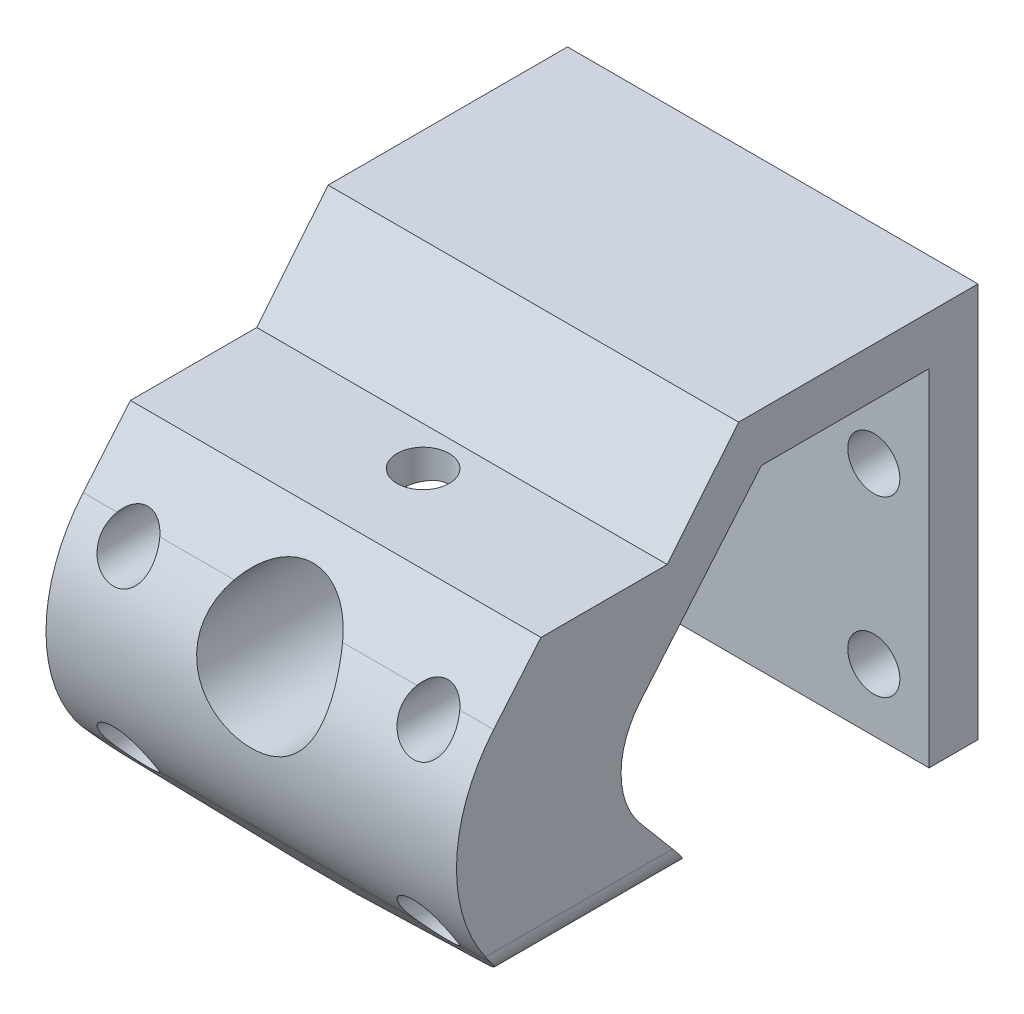
SolidWorks part; units mm, degrees
ref_plane "前视基准面" through (0, 0, 0) normal (0, 0, 1) x (1, 0, 0)
ref_plane "上视基准面" through (0, 0, 0) normal (0, 1, 0) x (1, 0, 0)
ref_plane "右视基准面" through (0, 0, 0) normal (1, 0, 0) x (0, 0, -1)
sketch "草图1" plane through (0, 0, 0) normal (1, 0, 0) x (0, 0, -1)
  line L0 (14.1075, 12.25) -> (3.7806, 12.25)
  line L1 (3.7806, 12.25) -> (-3.8242, 3.2211)
  line L2 (-3.8242, -3.2211) -> (3.7806, -12.25)
  line L3 (3.7806, -12.25) -> (14.1075, -12.25)
  line L4 (14.1075, -12.25) -> (14.1075, -9.25)
  line L5 (14.1075, -9.25) -> (9.3075, -9.25)
  line L6 (9.3075, -9.25) -> (9.3075, 9.25)
  line L7 (9.3075, 9.25) -> (14.1075, 9.25)
  line L8 (14.1075, 9.25) -> (14.1075, 12.25)
  line L9 (0, 0) -> (9.3075, 0) construction
  line L10 (14.3075, 12.45) -> (3.6876, 12.45)
  line L11 (3.6876, 12.45) -> (-3.9772, 3.3499)
  line L12 (-3.9772, -3.3499) -> (3.6876, -12.45)
  line L13 (3.6876, -12.45) -> (14.3075, -12.45)
  line L14 (14.3075, -12.45) -> (14.3075, -9.05)
  line L15 (14.3075, -9.05) -> (9.5075, -9.05)
  line L16 (9.5075, -9.05) -> (9.5075, 9.05)
  line L17 (9.5075, 9.05) -> (14.3075, 9.05)
  line L18 (14.3075, 9.05) -> (14.3075, 12.45)
  line L19 (0, -0.2) -> (9.3075, -0.2)
  line L20 (17.4075, 15.55) -> (2.2455, 15.55)
  line L21 (2.2455, 15.55) -> (-6.3482, 5.347)
  line L22 (-6.3482, -5.347) -> (2.2455, -15.55)
  line L23 (2.2455, -15.55) -> (17.4075, -15.55)
  line L24 (17.4075, -15.55) -> (17.4075, -5.95)
  line L28 (17.4075, 5.95) -> (17.4075, 15.55)
  line L29 (12.6075, 5.95) -> (17.4075, 5.95) construction
  line L30 (17.4075, -5.95) -> (12.6075, -5.95) construction
  line L31 (12.6075, -5.95) -> (12.6075, 5.95) construction
  line L32 (17.4075, 5.95) -> (17.4075, -5.95)
  line L33 (14.3075, 9.05) -> (14.3075, -9.05)
  line L34 (2.2455, 15.55) -> (-5.5992, 15.55)
  line L35 (-5.5992, 15.55) -> (-13.2705, 6.4421)
  line L36 (-13.2705, -6.4421) -> (-5.5992, -15.55)
  line L37 (-5.5992, -15.55) -> (2.2455, -15.55)
  line L38 (-10.2738, 10) -> (-2.2738, 10)
  line L39 (-2.2738, -10) -> (2.2455, -15.55)
  line L40 (-10.2738, -10) -> (-2.2738, -10)
  line L41 (-2.2738, 10) -> (2.2455, 15.55)
  arc A0 (-3.8242, 3.2211) -> (-3.8242, -3.2211) centre (0, 0) ccw
  arc A1 (-3.9772, 3.3499) -> (-3.9772, -3.3499) centre (0, 0) ccw
  arc A2 (-6.3482, 5.347) -> (-6.3482, -5.347) centre (0, 0) ccw
  arc A3 (-13.2705, 6.4421) -> (-13.2705, -6.4421) centre (-5.622, 0) ccw
  point P44 (-18.6966, 0)
  dimension "D5" = 5
  dimension "D10" = 10
  dimension "D1" = 3
  dimension "D2" = 10.3268
  dimension "D3" = 18.5
  dimension "D4" = 11.8049
  dimension "D6" = 4.8
  dimension "D9" = 6
  dimension "D11" = 8
  dimension "D12" = 20
  dimension "D7" = 0.2
  dimension "D8" = 3.3
extrude "凸台-拉伸1" add sketch "草图1" along normal blind 26 contours L21 A2 L22 L23 L24 L32 L28 L20 A1 L11 L10 L18 L33 L14 L13 L12 | A2 L21 L34 L35 L36 L37 L22 region at (0, 10.75, -17.004) region at (0, 0, 9.917)
sketch "草图2" plane through (0, 0, -17.4075) normal (0, 0, -1) x (-1, 0, 0)
  line L6 (-26, -9) -> (0, -9)
  line L7 (-26, -9) -> (-26, 9)
  line L8 (-26, 9) -> (0, 9)
  line L9 (0, -9) -> (0, 9)
  line L10 (-13, 9) -> (-13, -9) construction
  line L11 (-26, 0) -> (0, 0) construction
  line L12 (-26, 15.55) -> (0, 15.55) construction
  line L13 (-26, -15.55) -> (0, -15.55) construction
  line L14 (-26, -15.55) -> (-26, 15.55) construction
  line L15 (0, -15.55) -> (0, 15.55) construction
  circle A0 centre (-22.5, 5.5) radius 1.65
  circle A1 centre (-22.5, -5.5) radius 1.65
  circle A2 centre (-3.5, -5.5) radius 1.65
  circle A3 centre (-3.5, 5.5) radius 1.65
  point P12 (-3.5, -5.5)
  dimension "D3" = 3.3
  dimension "D1" = 18
  dimension "D2" = 26
  dimension "D4" = 11
  dimension "D5" = 19
extrude "切除-拉伸1" cut sketch "草图2" against normal through all contours A0 | A3 | A1 | A2
sketch "草图3" plane through (0, 0, 0) normal (-1, 0, 0) x (0, 0, 1)
  line L0 (-17.4075, -15.55) -> (-17.4075, 15.55) construction
  line L1 (-17.4075, -15.55) -> (10.737, -15.55)
  line L2 (-17.4075, -15.55) -> (-17.4075, -9.45)
  line L3 (-17.4075, -9.45) -> (10.737, -9.45)
  line L4 (10.737, -15.55) -> (10.737, -9.45)
  line L5 (-2.2455, -15.55) -> (-17.4075, -15.55) construction
  line L8 (-3.6876, -12.45) -> (-14.3075, -12.45) construction
  line L9 (13.2705, -6.4421) -> (10.2738, -10) construction
  dimension "D1" = 3.1
  dimension "D2" = 6.1
extrude "切除-拉伸2" cut sketch "草图3" against normal through all
ref_plane "基准面2" through (0, 0, 15.622) normal (0, 0, 1) x (1, 0, 0)
sketch "草图5" plane through (0, 0, 15.622) normal (0, 0, 1) x (1, 0, 0)
  line L0 (13, 6.4421) -> (13, -6.4421) construction
  line L1 (21.1454, 6.4421) -> (4.8546, 6.4421) construction
  line L2 (21.1454, -6.4421) -> (4.8546, -6.4421) construction
  line L3 (26, 10) -> (0, 10) construction
  circle A0 centre (13, 4.2) radius 4.1
  dimension "D1" = 5.8
  dimension "D2" = 8.2
extrude "切除-拉伸4" cut sketch "草图5" against normal up to next
sketch "草图6" plane through (0, -9.45, 0) normal (0, -1, 0) x (1, 0, 0)
  line L0 (13, 13.2705) -> (13, 10.737) construction
  line L1 (21.1454, 13.2705) -> (4.8546, 13.2705) construction
  line L2 (26, 10.737) -> (0, 10.737) construction
  circle A0 centre (13, 4.737) radius 1.65
  dimension "D1" = 3.3
  dimension "D2" = 6
extrude "切除-拉伸5" cut sketch "草图6" against normal through all
chamfer "倒角1" distance 2 angle 80 2 edges at (0, -9.45, 4.7881) (26, -9.45, 4.7881) first distance on face at (0, 2.7286, -0.655) first distance on face at (26, 2.7286, -0.655)
fillet "圆角1" radius 2 2 edges at (26, -7.45, 6.4727) (0, -7.45, 6.4727)
